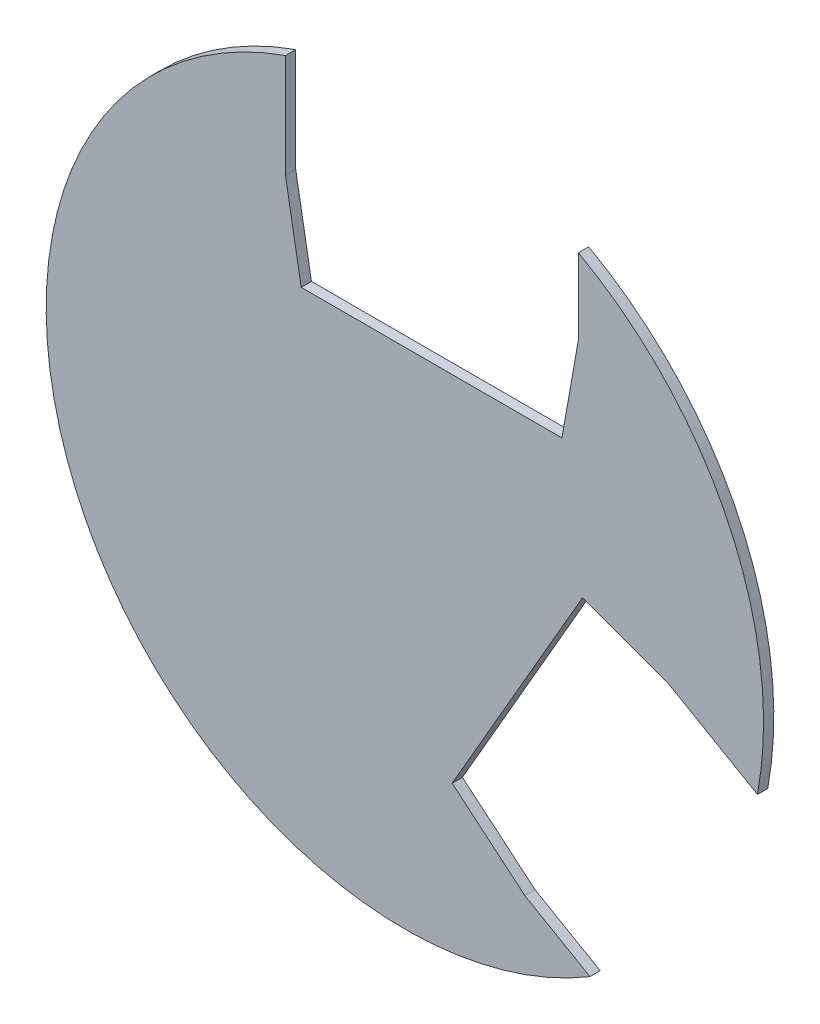
SolidWorks part; units mm, degrees
material "Balsa"
ref_plane "Plan de face" through (0, 0, 0) normal (0, 0, 1) x (1, 0, 0)
ref_plane "Plan de dessus" through (0, 0, 0) normal (0, 1, 0) x (1, 0, 0)
ref_plane "Plan de droite" through (0, 0, 0) normal (1, 0, 0) x (0, 0, -1)
sketch "Esquisse1" plane through (0, 0, 0) normal (0, 0, 1) x (1, 0, 0)
  circle A0 centre (0, 0) radius 175
extrude "Boss.-Extru.1" add sketch "Esquisse1" along normal blind 5
sketch "Esquisse2" plane through (0, 0, 0) normal (0, 0, -1) x (-1, 0, 0)
  line L0 (58.2408, 114.332) -> (58.2408, 213.8766)
  line L1 (58.2408, 213.8766) -> (-84.6817, 213.8766)
  line L2 (-84.6817, 213.8766) -> (-84.6817, 116.5135)
  line L3 (0, 0) -> (-290.6498, 0) construction
  line L4 (-84.6817, 116.5135) -> (-76.6366, 70.8876)
  line L5 (-76.6366, 70.8876) -> (50.5804, 70.8876)
  line L6 (50.5804, 70.8876) -> (58.2408, 114.332)
  line L7 (-128.1349, -6.728) -> (-214.343, -56.5003)
  line L8 (-214.343, -56.5003) -> (-142.8818, -180.2748)
  line L9 (-142.8818, -180.2748) -> (-58.5628, -131.5932)
  line L10 (-58.5628, -131.5932) -> (-23.0722, -101.8131)
  line L11 (-23.0722, -101.8131) -> (-86.6807, 8.3601)
  line L12 (-86.6807, 8.3601) -> (-128.1349, -6.728)
  point P16 (0, 0)
  point P43 (0, 0)
  dimension "D5" = 142.989
  dimension "D6" = 99.5446
  dimension "D1" = 127.217
  dimension "D2" = 100
  dimension "D3" = 100
  dimension "D4" = 142.9225
  dimension "D7" = 70.8876
  dimension "D8" = 50.5804
extrude "Enlèv. mat.-Extru.1" cut sketch "Esquisse2" against normal blind 5
